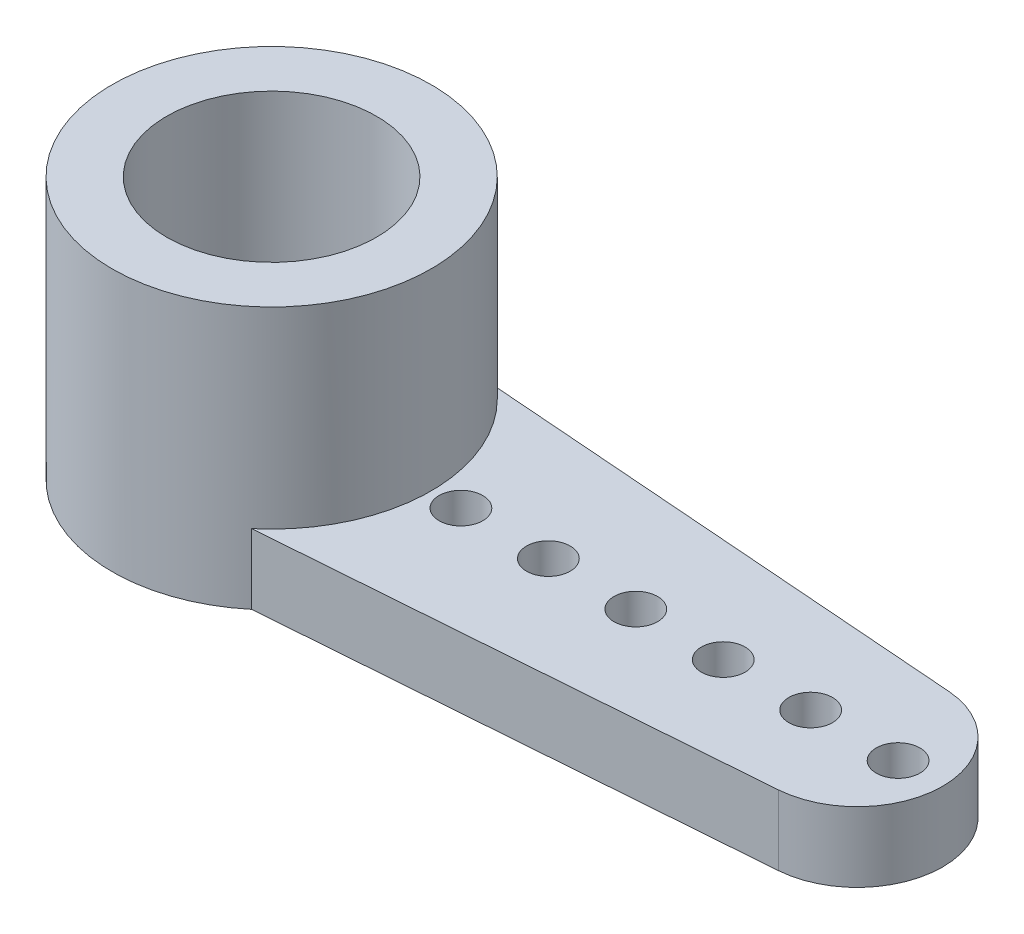
SolidWorks part; units mm, degrees
note: The reader was unsure of these and kept them because the rebuilt part matched: shared geometry of "Sketch1<3>", "Sketch1<4>".
ref_plane "Front" through (0, 0, 0) normal (0, 0, 1) x (1, 0, 0)
ref_plane "Top" through (0, 0, 0) normal (0, 1, 0) x (1, 0, 0)
ref_plane "Right" through (0, 0, 0) normal (1, 0, 0) x (0, 0, -1)
sketch "Sketch1" plane through (0, 0, 0) normal (0, 1, 0) x (1, 0, 0)
  line L0 (-15.3201, 2.8) -> (-4.1192, 1.95)
  line L1 (-17.6616, 0) -> (-4.1192, 0) construction
  line L2 (-4.1192, -1.95) -> (-15.3201, -2.8)
  line L3 (-21.3116, 0) -> (0, 0) construction
  line L4 (-15.3201, 2.8) -> (-15.3201, -2.8) construction
  circle A0 centre (-17.6616, 0) radius 3.65
  arc A1 (-4.1192, 1.95) -> (-4.1192, -1.95) centre (-4.2672, 0) cw
  circle A2 centre (-3.3314, 0) radius 0.5
  circle A3 centre (-5.3314, 0) radius 0.5
  circle A4 centre (-7.3314, 0) radius 0.5
  circle A5 centre (-9.3314, 0) radius 0.5
  circle A6 centre (-11.3314, 0) radius 0.5
  circle A7 centre (-13.3314, 0) radius 0.5
  circle A8 centre (-17.6616, 0) radius 2.4
  circle A9 centre (-17.6616, 0) radius 1.6
  point P13 (-2.3116, 0)
  dimension "D1" = 7.3
  dimension "D2" = 3.9
  dimension "D5" = 1
  dimension "D7" = 4.8
  dimension "D8" = 3.2
  dimension "D3" = 5.6
  dimension "D6" = 19
  dimension "D4" = 6
extrude "Boss-Extrude1" add sketch "Sketch1" along normal blind 1.6 contours A0 A8 | A9 | A8 A9 | A1 L0 A0 L2 A7 A6 A5 A4 A3 A2
extrude "Boss-Extrude2" add sketch "Sketch1<3>" along normal blind 6 contours A0 A8
sketch "Sketch1<3>" plane through (0, 0, 0) normal (0, 1, 0) x (1, 0, 0) same geometry as "Sketch1"
extrude "Cut-Extrude1" cut sketch "Sketch1<4>" along normal blind 1 contours A8 A9
sketch "Sketch1<4>" plane through (0, 0, 0) normal (0, 1, 0) x (1, 0, 0) same geometry as "Sketch1"
